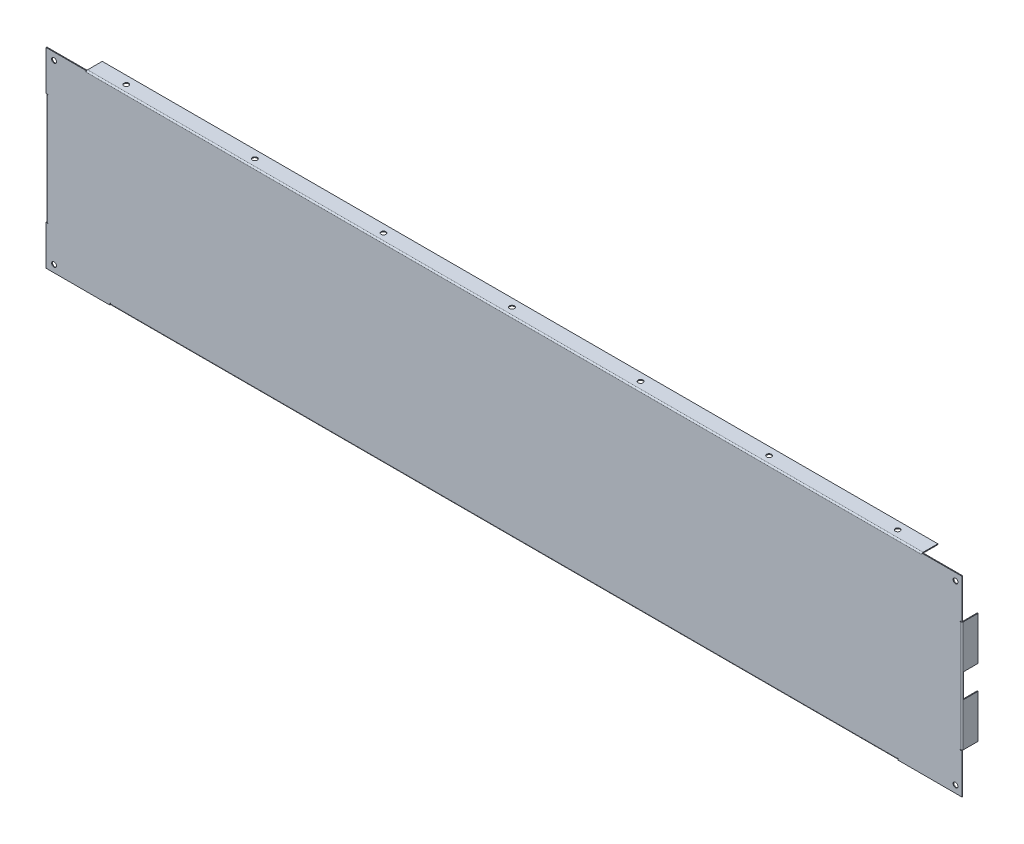
SolidWorks part; units mm, degrees
note: The reader was unsure of these and kept them because the rebuilt part matched: flange length of "边线-法兰1", "边线-法兰2", "边线-法兰3", "边线-法兰4".
ref_plane "前视基准面" through (0, 0, 0) normal (0, 0, 1) x (1, 0, 0)
ref_plane "上视基准面" through (0, 0, 0) normal (0, 1, 0) x (1, 0, 0)
ref_plane "右视基准面" through (0, 0, 0) normal (1, 0, 0) x (0, 0, -1)
sketch "草图1" plane through (0, 0, 0) normal (0, 0, 1) x (1, 0, 0)
  line L1 (-570, -119) -> (570, -119)
  line L2 (-570, -119) -> (-570, 119)
  line L3 (-570, 119) -> (570, 119)
  line L4 (570, -119) -> (570, 119)
  line L5 (-570, -119) -> (570, 119) construction
  line L6 (-570, 119) -> (570, -119) construction
  point P0 (0, 0)
  dimension "D1" = 1140
  dimension "D2" = 238
sheet metal parameters "钣金1" thickness 1 parameters "D1"=0.7366
base flange "基体-法兰1" sketch "草图1" thickness 1 reverse thickness direction no parameters "D1"=0.7366
edge flange "边线-法兰1" sketch "草图5" flange angle 90 flange length 20 flange position material inside bend radius 0.7366 thickness 1 relief rectangular parameters "D6"=10
sketch "草图5" plane through (570, 0, -1) normal (1, 0, 0) x (0, -1, 0)
  line L2 (-69, 0) -> (-69, 19)
  line L3 (-69, 19) -> (-15, 19)
  line L4 (69, 19) -> (69, 0)
  line L5 (119, 0) -> (-119, 0) construction
  line L6 (69, 0) -> (-69, 0)
  line L7 (-119, 0) -> (-119, -1) construction
  line L8 (119, 0) -> (119, -1) construction
  line L9 (119, -1) -> (-119, -1) construction
  line L10 (0, 0) -> (0, 29.3109) construction
  line L12 (-15, 19) -> (-15, 1)
  line L13 (-15, 1) -> (15, 1)
  line L14 (15, 19) -> (15, 1)
  line L15 (15, 19) -> (69, 19)
  dimension "D1" = 50
  dimension "D2" = 50
  dimension "D3" = 20
  dimension "D4" = 30
  dimension "D5" = 2
bend "边线折弯1" bend radius 0.7366 bend angle 90 parameters "D5"=1
edge flange "边线-法兰2" sketch "草图8" flange angle 90 flange length 20 flange position material inside bend radius 0.7366 thickness 1 relief rectangular parameters "D6"=10
sketch "草图8" plane through (-570, 0, -1) normal (-1, 0, 0) x (0, 1, 0)
  line L2 (-69, 0) -> (-69, 19)
  line L3 (-69, 19) -> (-15, 19)
  line L4 (69, 19) -> (69, 0)
  line L5 (119, 0) -> (-119, 0) construction
  line L6 (69, 0) -> (-69, 0)
  line L7 (-119, 0) -> (-119, -1) construction
  line L8 (119, 0) -> (119, -1) construction
  line L9 (0, 0) -> (0, 26.8309) construction
  line L10 (15, 19) -> (69, 19)
  line L11 (119, -1) -> (-119, -1) construction
  line L12 (-15, 19) -> (-15, 1)
  line L13 (-15, 1) -> (15, 1)
  line L14 (15, 19) -> (15, 1)
  dimension "D1" = 50
  dimension "D2" = 50
  dimension "D3" = 30
  dimension "D4" = 2
bend "边线折弯2" bend radius 0.7366 bend angle 90 parameters "D5"=2
edge flange "边线-法兰3" sketch "草图11" flange angle 90 flange length 20 flange position material inside bend radius 0.7366 thickness 1 relief rectangular parameters "D6"=10
sketch "草图11" plane through (0, -119, -1) normal (0, -1, 0) x (-1, 0, 0)
  line L2 (-490, 0) -> (-490, 19)
  line L3 (-490, 19) -> (490, 19)
  line L4 (490, 19) -> (490, 0)
  line L5 (570, 0) -> (-570, 0) construction
  line L6 (490, 0) -> (-490, 0)
  line L7 (570, -1) -> (-570, -1) construction
  line L8 (570, 0) -> (570, -1) construction
  line L9 (-570, 0) -> (-570, -1) construction
  dimension "D1" = 20
  dimension "D2" = 80
  dimension "D3" = 80
bend "边线折弯3" bend radius 0.7366 bend angle 90 parameters "D5"=3
edge flange "边线-法兰4" sketch "草图14" flange angle 90 flange length 20 flange position material inside bend radius 0.7366 thickness 1 relief rectangular parameters "D6"=10
sketch "草图14" plane through (0, 119, -1) normal (0, 1, 0) x (1, 0, 0)
  line L2 (-520, 0) -> (-520, 19)
  line L3 (-520, 19) -> (520, 19)
  line L4 (520, 19) -> (520, 0)
  line L5 (570, 0) -> (-570, 0) construction
  line L6 (520, 0) -> (-520, 0)
  line L7 (570, 0) -> (570, -1) construction
  line L8 (-570, 0) -> (-570, -1) construction
  line L9 (570, -1) -> (-570, -1) construction
  dimension "D1" = 50
  dimension "D2" = 50
  dimension "D3" = 20
bend "边线折弯4" bend radius 0.7366 bend angle 90 parameters "D5"=4
sketch "草图15" plane through (0, -119, 0) normal (0, -1, 0) x (1, 0, 0)
  line L0 (-490, -20) -> (490, -20) construction
  line L1 (-570, -20) -> (-570, -1.7366) construction
  circle A0 centre (-480, -10) radius 3
  circle A1 centre (-320, -10) radius 3
  circle A2 centre (-160, -10) radius 3
  circle A3 centre (0, -10) radius 3
  circle A4 centre (160, -10) radius 3
  circle A5 centre (320, -10) radius 3
  circle A6 centre (480, -10) radius 3
  dimension "D8" = 6
  dimension "D1" = 10
  dimension "D2" = 90
  dimension "D3" = 160
  dimension "D4" = 160
  dimension "D5" = 160
  dimension "D6" = 160
  dimension "D7" = 160
  dimension "D9" = 160
extrude "切除-拉伸1" cut sketch "草图15" against normal through all normal cut yes
sketch "草图18" plane through (0, 0, -1) normal (0, 0, -1) x (-1, 0, 0)
  circle A0 centre (-562, -110) radius 3
  circle A1 centre (-562, 110) radius 3
  circle A2 centre (560, 110) radius 3
  circle A3 centre (560, -110) radius 3
  dimension "D1" = 6
extrude "切除-拉伸2" cut sketch "草图18" against normal through all normal cut yes
flat pattern "平板型式1" [suppressed]
sketch "折弯-线1" plane through (0, 0, 0) normal (0, 1, 0) x (-1, 0, 0)
bend of the flat pattern "展开-<边线折弯1>1"
bend of the flat pattern "展开-<边线折弯2>1"
bend of the flat pattern "展开-<边线折弯3>1"
bend of the flat pattern "展开-<边线折弯4>1"
